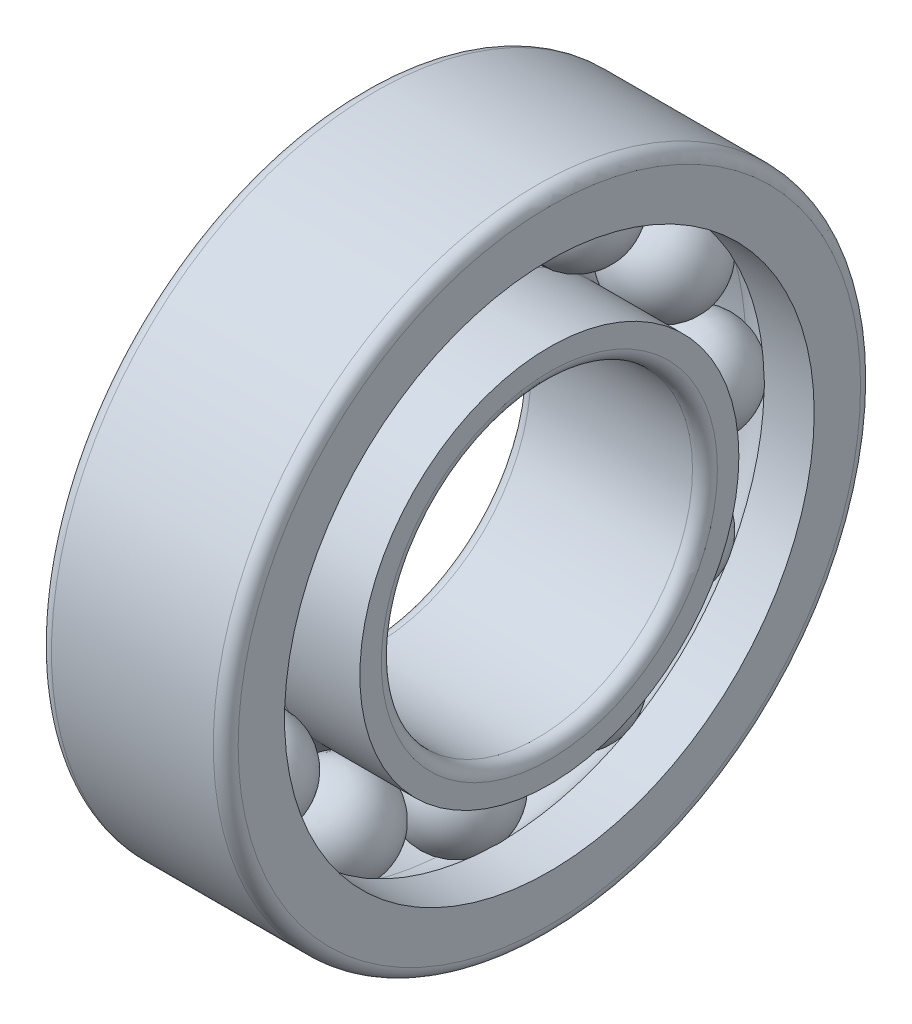
SolidWorks part; units mm, degrees
ref_plane "Plane1" through (0, 0, 0) normal (0, 0, 1) x (1, 0, 0)
ref_plane "Plane2" through (0, 0, 0) normal (0, 1, 0) x (1, 0, 0)
ref_plane "Plane3" through (0, 0, 0) normal (1, 0, 0) x (0, 0, -1)
sketch "Clipboard" plane through (0, 0, 0) normal (0, 0, 1) x (1, 0, 0)
  line L0 (-10, 0) -> (10, 0) construction
  line L1 (0, 0) -> (21.872, -4.649)
  line L2 (0, 0) -> (18.8293, 4.0023)
  line L3 (0, 0) -> (21.872, -4.649)
  line L4 (0, 0) -> (-22.3573, -0.3902)
  dimension "BallCLRad" = 19.25
sketch "CagSpiSke" plane through (0, 0, 0) normal (0, 0, 1) x (1, 0, 0)
  line L0 (1.0125, 18.575) -> (1.0125, 19.925)
  line L1 (1.0125, 19.925) -> (-1.0125, 19.925)
  line L2 (-1.0125, 19.925) -> (-1.0125, 18.575)
  line L3 (-1.0125, 18.575) -> (1.0125, 18.575)
  line L4 (-20.6375, 0) -> (20.6375, 0) construction
  line L5 (0, 0) -> (0, 23.7692) construction
  dimension "OD" = 39.85
  dimension "ID" = 37.15
revolve "CageSpine" add sketch "CagSpiSke" angle 0.001 about L4
ref_axis "Axis1" through (-50, 0, 0) along (1, 0, 0)
sketch "CagBalSke" plane through (0, 0, 0) normal (0, 0, 1) x (1, 0, 0)
  line L0 (-4.455, 19.25) -> (4.455, 19.25)
  line L1 (-1.905, 19.25) -> (1.905, 19.25) construction
  line L2 (-10, 0) -> (10, 0) construction
  line L3 (0, 0) -> (0, 24) construction
  arc A0 (4.455, 19.25) -> (-4.455, 19.25) centre (0, 19.25) cw
  dimension "BallCLRad" = 19.25
revolve "CageBall" [suppressed] add sketch "CagBalSke" angle 360 about L1 reverse direction yes
pattern_circular "CageBalls" [suppressed] count 12 every 30 about axis through (-50, 0, 0) along (1, 0, 0)
sketch "CagTrmODSke" plane through (0, 0, 0) normal (0, 0, 1) x (1, 0, 0)
  line L0 (4.456, 19.925) -> (4.456, 23.706)
  line L1 (4.456, 23.706) -> (-4.456, 23.706)
  line L2 (-4.456, 23.706) -> (-4.456, 19.925)
  line L3 (-4.456, 19.925) -> (4.456, 19.925)
  line L4 (-20.6375, 0) -> (20.6375, 0) construction
  line L5 (0, 0) -> (0, 25) construction
  dimension "Width" = 8.912
  dimension "ID" = 39.85
  dimension "OD" = 47.412
revolve "CageTrimOD" [suppressed] cut sketch "CagTrmODSke" angle 360 about L4 reverse direction yes
sketch "CagTrmIDSke" plane through (0, 0, 0) normal (0, 0, 1) x (1, 0, 0)
  line L0 (4.456, 14.796) -> (4.456, 18.575)
  line L1 (4.456, 18.575) -> (-4.456, 18.575)
  line L2 (-4.456, 18.575) -> (-4.456, 14.796)
  line L3 (-4.456, 14.796) -> (4.456, 14.796)
  line L4 (-20.6375, 0) -> (20.6375, 0) construction
  line L5 (0, 0) -> (0, 25) construction
  dimension "Width" = 8.912
  dimension "ID" = 29.592
  dimension "OD" = 37.15
revolve "CageTrimID" [suppressed] cut sketch "CagTrmIDSke" angle 360 about L4 reverse direction yes
sketch "BalSimSke" plane through (0, 0, 0) normal (0, 0, 1) x (1, 0, 0)
  line L0 (-10, 0) -> (10, 0) construction
  line L1 (-10, 19.25) -> (10, 19.25) construction
  line L2 (0, 0) -> (0, 23) construction
  circle A0 centre (0, 19.25) radius 4.05
  dimension "BallCLRad" = 19.25
  dimension "Ball_diameter" = 8.1
revolve "BallsSimplified" [suppressed] add sketch "BalSimSke" angle 360 about L0
sketch "BalDetSke" plane through (0, 0, 0) normal (0, 0, 1) x (1, 0, 0)
  line L0 (-4.05, 19.25) -> (4.05, 19.25)
  line L1 (-1.905, 19.25) -> (1.905, 19.25) construction
  line L2 (0, 0) -> (0, 25) construction
  arc A0 (4.05, 19.25) -> (-4.05, 19.25) centre (0, 19.25) cw
  dimension "BallCLRad" = 19.25
  dimension "Ball_diameter" = 8.1
revolve "BallDetailed" add sketch "BalDetSke" angle 360 about L1 reverse direction yes
sketch "InnRacSke" plane through (0, 0, 0) normal (0, 0, 1) x (1, 0, 0)
  line L0 (-3.4785, 17.225) -> (-7.5, 17.225)
  line L1 (-7.5, 17.225) -> (-7.5, 13.5)
  line L2 (-6.5, 12.5) -> (6.5, 12.5)
  line L3 (7.5, 13.5) -> (7.5, 15.225)
  line L4 (0, 15.225) -> (7.5, 15.225)
  line L5 (-20.6375, 0) -> (20.6375, 0) construction
  line L6 (0, 0) -> (0, 30) construction
  arc A0 (-7.5, 13.5) -> (-6.5, 12.5) centre (-6.5, 13.5) ccw
  arc A1 (6.5, 12.5) -> (7.5, 13.5) centre (6.5, 13.5) ccw
  arc A2 (0, 15.225) -> (-3.4785, 17.225) centre (0, 19.25) cw
  dimension "BallCLRad" = 19.25
  dimension "Fillet_radius" = 1
  dimension "Ball_diameter" = 8.05
  dimension "ID" = 25
  dimension "OD" = 34.45
  dimension "Width" = 15
revolve "InnerRace" add sketch "InnRacSke" angle 360 about L5 reverse direction yes
sketch "OutRacSke" plane through (0, 0, 0) normal (0, 0, 1) x (1, 0, 0)
  line L0 (0, 23.275) -> (-7.5, 23.275)
  line L1 (-7.5, 23.275) -> (-7.5, 25)
  line L2 (-6.5, 26) -> (6.5, 26)
  line L3 (7.5, 25) -> (7.5, 21.275)
  line L4 (7.5, 21.275) -> (3.4785, 21.275)
  line L5 (-20.6375, 0) -> (20.6375, 0) construction
  line L6 (0, 0) -> (0, 30) construction
  arc A0 (-7.5, 25) -> (-6.5, 26) centre (-6.5, 25) cw
  arc A1 (6.5, 26) -> (7.5, 25) centre (6.5, 25) cw
  arc A2 (3.4785, 21.275) -> (0, 23.275) centre (0, 19.25) ccw
  dimension "BallCLRad" = 19.25
  dimension "Fillet_radius" = 1
  dimension "Ball_diameter" = 8.05
  dimension "Width" = 15
revolve "OuterRace" add sketch "OutRacSke" angle 360 about L5 reverse direction yes
pattern_circular "BallsDetailed" count 12 every 30 about axis through (-50, 0, 0) along (1, 0, 0) of "BallDetailed"
equation "\"BallCLRad@Clipboard\" = ( \"OD@OutRacSke\" + \"ID@InnRacSke\" ) / 4"
equation "\"BallCLRad@BalSimSke\" = \"BallCLRad@Clipboard\""
equation "\"BallCLRad@BalDetSke\" = \"BallCLRad@Clipboard\""
equation "\"BallCLRad@InnRacSke\" = \"BallCLRad@Clipboard\""
equation "\"BallCLRad@OutRacSke\" = \"BallCLRad@Clipboard\""
equation "\"Ball_diameter@InnRacSke\" = \"Ball_diameter@BalDetSke\" - 0.05"
equation "\"Ball_diameter@OutRacSke\" = \"Ball_diameter@BalDetSke\" - 0.05"
equation "\"Ball_diameter@BalSimSke\" = \"Ball_diameter@BalDetSke\""
equation "\"Width@OutRacSke\" = \"Width@InnRacSke\""
equation "\"Fillet_radius@OutRacSke\" = \"Fillet_radius@InnRacSke\""
equation "\"Max_count@Clipboard\" = int( 3.14159265 / atn(( \"Ball_diameter@BalDetSke\" / 2) / sqr( \"BallCLRad@Clipboard\"  *  \"BallCLRad@Clipboard\" - ( \"Ball_diameter@BalDetSke\" / 2) *  ( \"Ball_diameter@BalDetSke\" / 2))))"
equation "\"Max_count@Clipboard\" = ((sgn( \"Max_count@Clipboard\" - \"Count@Clipboard\" )-1)*( \"Max_count@Clipboard\" - \"Count@Clipboard\" ))/-2+ \"Count@Clipboard\""
equation "\"Count@BallsDetailed\" = int( \"Show_count@Clipboard\" ) "
equation "\"Count@BallsDetailed\" = ((sgn( \"Count@BallsDetailed\" - \"Max_count@Clipboard\" )-1)*( \"Count@BallsDetailed\" - \"Max_count@Clipboard\" ))/-2+ \"Max_count@Clipboard\""
equation "\"Count@BallsDetailed\" = ((sgn( \"Count@BallsDetailed\" - \"Min_count@Clipboard\" )+1)*( \"Count@BallsDetailed\" - \"Min_count@Clipboard\"))/2 +\"Min_count@Clipboard\""
equation "\"Angle@BallsDetailed\" = 360.0 / \"Max_count@Clipboard\""
equation "\"BallCLRad@CagBalSke\" = \"BallCLRad@Clipboard\""
equation "\"Count@CageBalls\" = \"Count@BallsDetailed\""
equation "\"Angle@CageBalls\" = \"Angle@BallsDetailed\""
equation "\"Angle@CageSpine\" =  \"Angle@CageBalls\" * ( \"Count@CageBalls\" -1 + int( \"Count@CageBalls\" / \"Max_count@Clipboard\" ) )  + 0.001 -  int( \"Count@CageBalls\" / \"Max_count@Clipboard\" ) * 0.001"
equation "\"Angle@CageSpine\" =  \"Angle@CageSpine\" * int( \"Min_count@Clipboard\" / 2) + int(1 / \"Min_count@Clipboard\")  * 0.001"
equation "\"CageWallOD@CagBalSke\" =  \"Ball_diameter@BalDetSke\" * 1.1"
equation "\"Thickness@CagSpiSke\" =  \"Ball_diameter@BalDetSke\" * 0.25"
equation "\"OD@CagTrmODSke\" = \"BallCLRad@Clipboard\" * 2 + \"CageWallOD@CagBalSke\" + 0.002"
equation "\"ID@CagTrmODSke\" = \"BallCLRad@Clipboard\" * 2 + \"Ball_diameter@BalDetSke\" / 6"
equation "\"OD@CagTrmIDSke\" = \"BallCLRad@Clipboard\" * 2 - \"Ball_diameter@BalDetSke\" / 6"
equation "\"ID@CagTrmIDSke\" = \"BallCLRad@Clipboard\" * 2 - \"CageWallOD@CagBalSke\" + 0.002"
equation "\"OD@CagSpiSke\" = \"ID@CagTrmODSke\""
equation "\"ID@CagSpiSke\" = \"OD@CagTrmIDSke\""
equation "\"Width@CagTrmODSke\" = \"CageWallOD@CagBalSke\" + 0.002"
equation "\"Width@CagTrmIDSke\" = \"CageWallOD@CagBalSke\" + 0.002"
